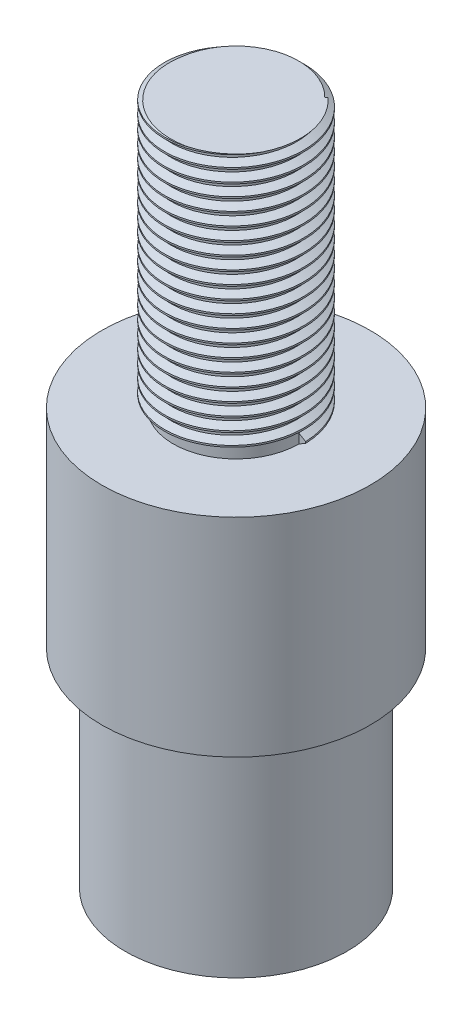
SolidWorks part; units mm, degrees
ref_plane "Front Plane" through (0, 0, 0) normal (0, 0, 1) x (1, 0, 0)
ref_plane "Top Plane" through (0, 0, 0) normal (0, 1, 0) x (1, 0, 0)
ref_plane "Right Plane" through (0, 0, 0) normal (1, 0, 0) x (0, 0, -1)
sketch "Sketch1" plane through (0, 0, 0) normal (0, 1, 0) x (1, 0, 0)
  circle A0 centre (0, 0) radius 13.4493
  dimension "D1" = 26.8986
extrude "Boss-Extrude1" add sketch "Sketch1" along normal blind 20.828 contours A0
sketch "Sketch2" plane through (0, 0, 0) normal (0, -1, 0) x (-1, 0, 0)
  circle A0 centre (0, 0) radius 11.1125
  dimension "D1" = 22.225
extrude "Boss-Extrude2" add sketch "Sketch2" along normal blind 20.828 contours A0
sketch "Sketch3" plane through (0, 20.828, 0) normal (0, 1, 0) x (1, 0, 0)
  circle A0 centre (0, 0) radius 6.2928
  dimension "D1" = 12.5857
extrude "Boss-Extrude3" add sketch "Sketch3" along normal blind 26.9621
thread "Thread1" pitch 1.27 method extrude trim with end face yes profile "Thread Profile2" start angle 0, offset 0, length 0, pitch 1.27, diameter 12.5857
ref_plane "Plane2" through (6.2928, 20.828, 0) normal (0, 0, 1) x (1, 0, 0)
sketch "Thread Profile2" plane through (6.2928, 20.828, 0) normal (0, 0, 1) x (1, 0, 0)
  line L0 (0, 0) -> (0, 1.27) construction
  line L1 (0, 0) -> (0.6874, 0.3969)
  line L2 (0.6874, 0.3969) -> (0.6874, 0.5556)
  line L3 (0.6874, 0.5556) -> (0, 0.9525)
  line L4 (0.6874, 0.4762) -> (0, 0.4762) construction
  line L11 (0, 0) -> (0, 0.9525)
  point P2 (0, 0)
  dimension "Pitch" = 1.27
  dimension "Profile_Angle" = 60
  dimension "Profile_Land" = 0.1588
  dimension "Profile_Height" = 0.6874
